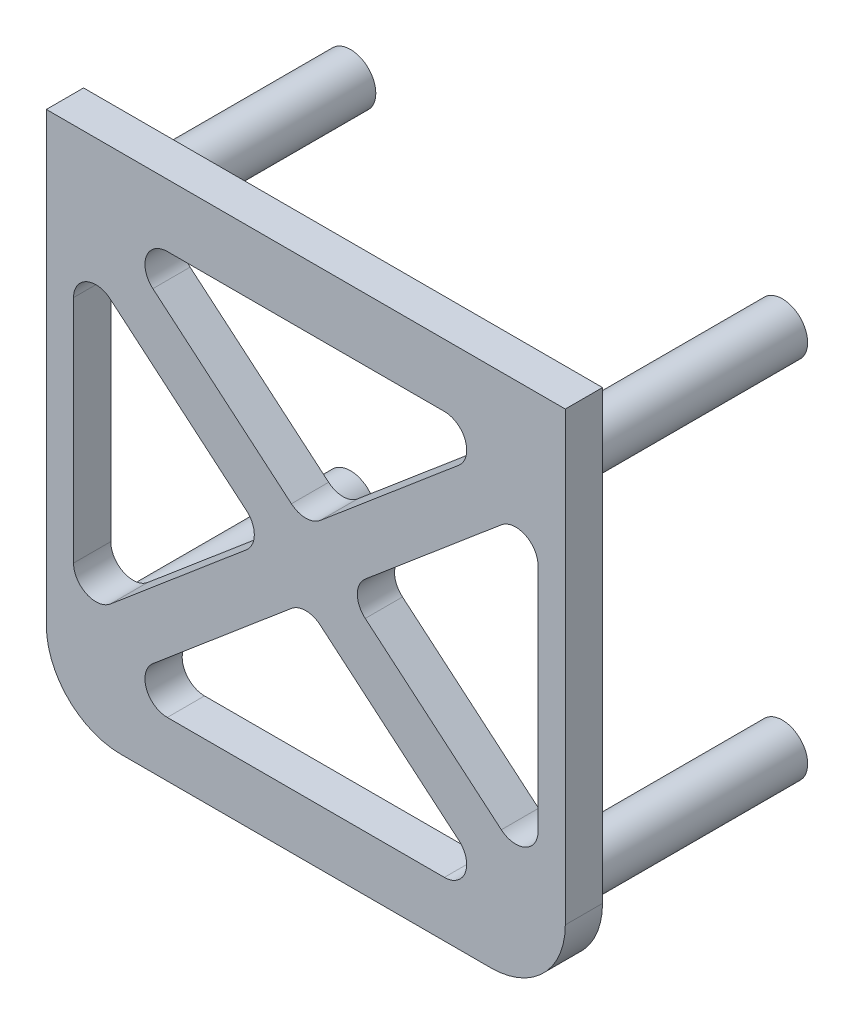
SolidWorks part; units mm, degrees
ref_plane "Front Plane" through (0, 0, 0) normal (0, 0, 1) x (1, 0, 0)
ref_plane "Top Plane" through (0, 0, 0) normal (0, 1, 0) x (1, 0, 0)
ref_plane "Right Plane" through (0, 0, 0) normal (1, 0, 0) x (0, 0, -1)
sketch "Sketch1" plane through (0, 0, 0) normal (0, 0, 1) x (1, 0, 0)
  circle A0 centre (29, -40) radius 3.4 construction
  circle A1 centre (-29, -40) radius 3.4 construction
  circle A2 centre (-29, 9) radius 3.4 construction
  circle A3 centre (29, 9) radius 3.4 construction
  circle A4 centre (29, -40) radius 3.4
  circle A5 centre (-29, -40) radius 3.4
  circle A6 centre (-29, 9) radius 3.4
  circle A7 centre (29, 9) radius 3.4
extrude "Boss-Extrude1" add sketch "Sketch1" along normal blind 30
sketch "Sketch2" plane through (0, 0, 30) normal (0, 0, 1) x (1, 0, 0)
  line L1 (-40, -40) -> (-40, 55) construction
  line L2 (40, -50) -> (-40, -50) construction
  line L3 (40, -40) -> (40, 55) construction
  line L4 (-40, -40) -> (-40, 55)
  line L5 (40, -50) -> (-40, -50)
  line L6 (40, -40) -> (40, 55)
  line L7 (-24.85, -50) -> (24.85, -50)
  line L8 (-34.85, -40) -> (-34.85, 20)
  line L9 (-34.85, 20) -> (34.85, 20)
  line L10 (34.85, -40) -> (34.85, 20)
  arc A0 (24.85, -50) -> (34.85, -40) centre (24.85, -40) ccw
  arc A1 (-24.85, -50) -> (-34.85, -40) centre (-24.85, -40) cw
  point P8 (0, 20)
  point P9 (0, -50)
  point P14 (34.85, -50)
  point P17 (-34.85, -50)
  circle M6 centre (-29, 9) radius 3.4
  dimension "D3" = 10
  dimension "D1" = 5.15
  dimension "D2" = 70
extrude "Boss-Extrude2" add sketch "Sketch2" along normal blind 5 contours L5 L10 L9 L8 M6 | M6 region at (0.2194, -14.8886, 30) region at (-29, 9, 30)
sketch "Sketch3" plane through (0, 0, 30) normal (0, 0, -1) x (-1, 0, 0)
  line L0 (-26.8058, 11.5972) -> (31.1942, -37.4028)
  line L1 (26.8058, -42.5972) -> (-31.1942, 6.4028)
  line L2 (31.1942, 6.4028) -> (-26.8058, -42.5972)
  line L3 (-31.1942, -37.4028) -> (26.8058, 11.5972)
  line L4 (-31.1942, 6.4028) -> (-31.1942, -37.4028)
  line L5 (-26.8058, -42.5972) -> (26.8058, -42.5972)
  line L6 (31.1942, 6.4028) -> (31.1942, -37.4028)
  line L7 (26.8058, 11.5972) -> (-26.8058, 11.5972)
  circle A0 centre (29, 9) radius 3.4 construction
  circle A1 centre (29, -40) radius 3.4 construction
  circle A2 centre (-29, -40) radius 3.4 construction
  circle A3 centre (-29, 9) radius 3.4 construction
  circle A4 centre (29, 9) radius 3.4
  circle A5 centre (29, -40) radius 3.4
  circle A6 centre (-29, -40) radius 3.4
  circle A7 centre (-29, 9) radius 3.4
extrude "Cut-Extrude1" cut sketch "Sketch3" against normal up to next contours L1 L4 L3 | L3 L7 L0 | L6 L2 L0 | L2 L5 L1 region at (0, 4.0485, 30) region at (22.5523, -15.5, 30) region at (-22.5523, -15.5, 30) region at (0, -35.0485, 30)
fillet "Fillet1" radius 3 12 edges at (31.1942, 6.4028, 32.5) (5.2684, -15.5, 32.5) (31.1942, -37.4028, 32.5) (26.8058, -42.5972, 32.5) (0, -19.9509, 32.5) (-26.8058, -42.5972, 32.5) (-31.1942, -37.4028, 32.5) (-5.2684, -15.5, 32.5) (-31.1942, 6.4028, 32.5) (-26.8058, 11.5972, 32.5) (0, -11.0491, 32.5) (26.8058, 11.5972, 32.5)
